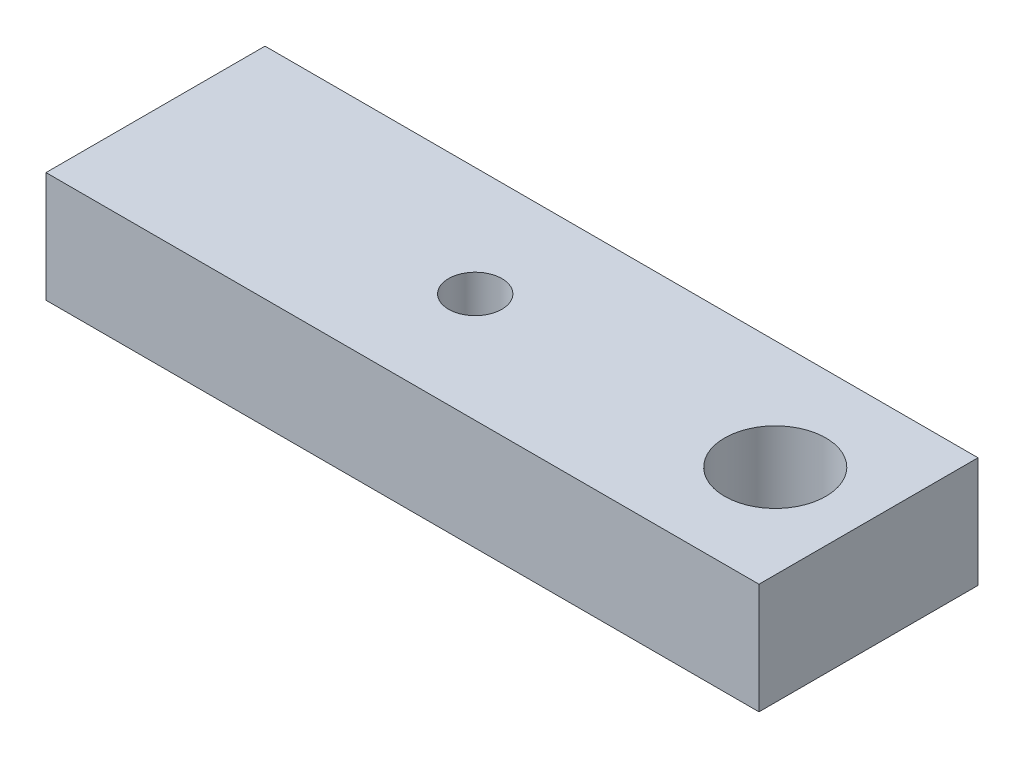
SolidWorks part; units mm, degrees
material "Polyurethane Foam Flexible"
ref_plane "Front Plane" through (0, 0, 0) normal (0, 0, 1) x (1, 0, 0)
ref_plane "Top Plane" through (0, 0, 0) normal (0, 1, 0) x (1, 0, 0)
ref_plane "Right Plane" through (0, 0, 0) normal (1, 0, 0) x (0, 0, -1)
sketch "Sketch1" plane through (0, 0, 0) normal (0, 1, 0) x (1, 0, 0)
  line L1 (0, 0) -> (33.9852, 0)
  line L2 (0, 0) -> (0, 10.4394)
  line L3 (0, 10.4394) -> (33.9852, 10.4394)
  line L4 (33.9852, 0) -> (33.9852, 10.4394)
  dimension "D1" = 33.9852
  dimension "D2" = 10.4394
extrude "Boss-Extrude1" add sketch "Sketch1" along normal blind 5.2705
sketch "Sketch2" plane through (0, 5.2705, 0) normal (0, 1, 0) x (1, 0, 0)
  line L0 (33.9852, 0) -> (33.9852, 10.4394) construction
  line L1 (0, 10.4394) -> (0, 0) construction
  line L2 (33.9852, 5.2197) -> (0, 5.2197) construction
  circle A0 centre (29.5402, 5.2197) radius 2.413
  circle A1 centre (15.24, 5.2197) radius 1.27
  dimension "D1" = 4.826
  dimension "D2" = 2.54
  dimension "D3" = 4.445
  dimension "D5" = 15.24
extrude "Cut-Extrude1" cut sketch "Sketch2" against normal through all
sketch "Sketch3" plane through (0, 5.2705, 0) normal (0, 1, 0) x (1, 0, 0)
  line L0 (0, 8.3) -> (33.9852, 8.3) construction
  line L1 (33.9852, 0) -> (33.9852, 10.4394) construction
  line L2 (0, 10.4394) -> (0, 0) construction
  line L3 (33.9852, 10.4394) -> (0, 10.4394) construction
  line L4 (0, 0) -> (33.9852, 0) construction
  line L5 (0, 10.4394) -> (0, 0) construction
  text T0 "LIFT TO FILL\r\nLIFT TO FILL\r\nLIFT TO FILL" font "Century Gothic" height 1.651
